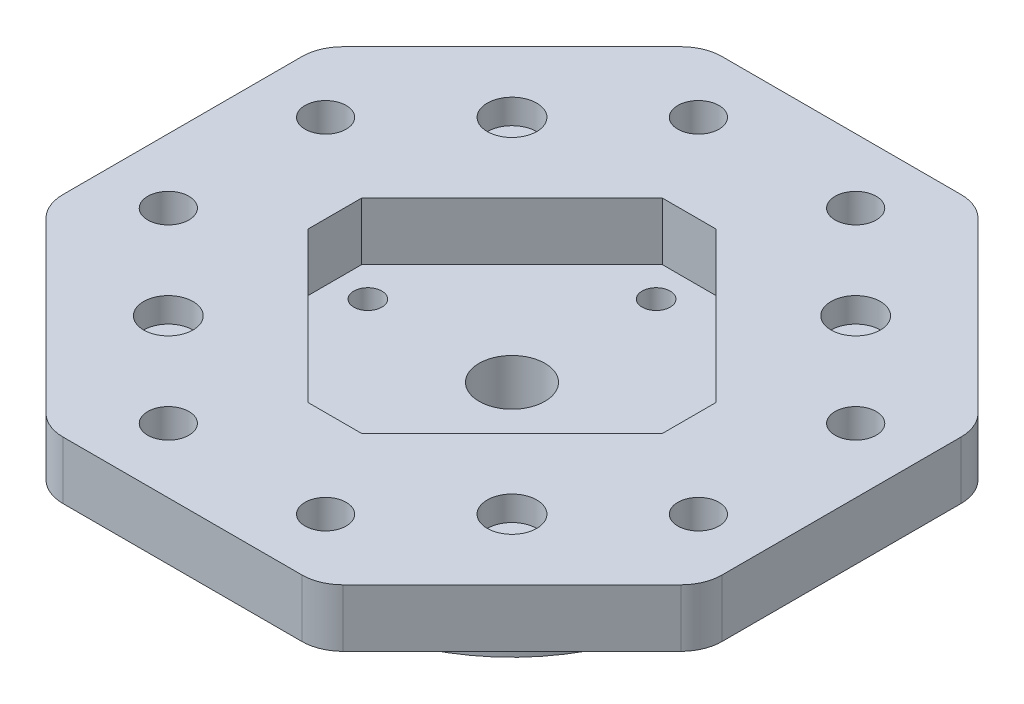
SolidWorks part; units mm, degrees
material "ABS"
ref_plane "Front" through (0, 0, 0) normal (0, 0, 1) x (1, 0, 0)
ref_plane "Top" through (0, 0, 0) normal (0, 1, 0) x (1, 0, 0)
ref_plane "Right" through (0, 0, 0) normal (1, 0, 0) x (0, 0, -1)
sketch "草图1" plane through (0, 0, 0) normal (0, 1, 0) x (1, 0, 0)
  circle A0 centre (0, 0) radius 27.5
  dimension "D1" = 55
extrude "凸台-拉伸1" add sketch "草图1" against normal blind 3
sketch "草图2" plane through (0, -3, 0) normal (0, -1, 0) x (1, 0, 0)
  circle A0 centre (0, 0) radius 22.5
  dimension "D1" = 45
extrude "凸台-拉伸2" add sketch "草图2" along normal blind 10
sketch "草图3" plane through (0, -13, 0) normal (0, -1, 0) x (1, 0, 0)
  circle A0 centre (0, 17.5) radius 1.7
  circle A1 centre (17.5, 0) radius 1.7
  circle A2 centre (0, -17.5) radius 1.7
  circle A3 centre (-17.5, 0) radius 1.7
  circle A4 centre (0, 0) radius 4
  point P12 (0, 0)
  dimension "D1" = 3.4
  dimension "D4" = 8
  dimension "D2" = 17.5
  dimension "D3" = 4
extrude "切除-拉伸1" cut sketch "草图3" against normal up to next
sketch "草图4" plane through (0, 0, 0) normal (0, 1, 0) x (1, 0, 0)
  line L0 (-66.0793, 0) -> (64.6468, 0) construction
  line L1 (0, 69.9547) -> (0, -71.394) construction
  line L2 (0, 21.5) -> (3.2487, 21.5)
  line L3 (3.2487, 21.5) -> (21.5, 3.2487)
  line L4 (21.5, 3.2487) -> (21.5, 0)
  line L5 (21.5, 0) -> (21.5, -3.2487)
  line L6 (21.5, -3.2487) -> (3.2487, -21.5)
  line L7 (3.2487, -21.5) -> (0, -21.5)
  line L8 (0, -21.5) -> (-3.2487, -21.5)
  line L9 (-3.2487, -21.5) -> (-21.5, -3.2487)
  line L10 (-21.5, -3.2487) -> (-21.5, 0)
  line L11 (-21.5, 0) -> (-21.5, 3.2487)
  line L12 (-21.5, 3.2487) -> (-3.2487, 21.5)
  line L13 (-3.2487, 21.5) -> (0, 21.5)
  line L18 (0, 40) -> (16.5685, 40)
  line L19 (16.5685, 40) -> (40, 16.5685)
  line L20 (40, 16.5685) -> (40, 0)
  line L21 (40, 0) -> (40, -16.5685)
  line L22 (16.5685, -40) -> (0, -40)
  line L23 (40, -16.5685) -> (16.5685, -40)
  line L24 (0, -40) -> (-16.5685, -40)
  line L25 (-40, -16.5685) -> (-40, 0)
  line L26 (-16.5685, -40) -> (-40, -16.5685)
  line L27 (-40, 0) -> (-40, 16.5685)
  line L28 (-16.5685, 40) -> (0, 40)
  line L29 (-40, 16.5685) -> (-16.5685, 40)
  circle A0 centre (0, 0) radius 27.5 construction
  point P24 (0, 0)
  point P29 (0, 0)
  point P40 (0, 0)
  dimension "D1" = 21.5
  dimension "D2" = 21.5
  dimension "D3" = 45
  dimension "D4" = 17.5
  dimension "D6" = 40
  dimension "D7" = 22.5
  dimension "D8" = 40
  dimension "D5" = 4
  dimension "D9" = 4
extrude "凸台-拉伸3" add sketch "草图4" along normal blind 7
sketch "草图6" plane through (0, 7, 0) normal (0, 1, 0) x (1, 0, 0)
  line L0 (0, 0) -> (42.1503, 42.1503) construction
  line L1 (21.5, 3.2487) -> (3.2487, 21.5) construction
  circle A0 centre (20.8597, 20.8597) radius 3
  circle A1 centre (20.8597, -20.8597) radius 3
  circle A2 centre (-20.8597, -20.8597) radius 3
  circle A3 centre (-20.8597, 20.8597) radius 3
  point P16 (0, 0)
  dimension "D1" = 6
  dimension "D2" = 12
extrude "切除-拉伸2" cut sketch "草图6" against normal blind 3
sketch "草图7" plane through (0, 7, 0) normal (0, 1, 0) x (1, 0, 0)
  line L0 (0, 0) -> (38.1237, 38.1237) construction
  line L1 (21.5, 3.2487) -> (3.2487, 21.5) construction
  line L3 (27.8626, 13.8567) -> (3.2196, 38.4997) construction
  circle A0 centre (9.5459, 32.1734) radius 2.5
  circle A1 centre (32.1734, 9.5459) radius 2.5
  circle A2 centre (32.1734, -9.5459) radius 2.5
  circle A3 centre (9.5459, -32.1734) radius 2.5
  circle A4 centre (-9.5459, -32.1734) radius 2.5
  circle A5 centre (-32.1734, -9.5459) radius 2.5
  circle A6 centre (-32.1734, 9.5459) radius 2.5
  circle A7 centre (-9.5459, 32.1734) radius 2.5
  point P24 (0, 0)
  dimension "D1" = 5
  dimension "D2" = 5
  dimension "D3" = 16
  dimension "D4" = 16
  dimension "D5" = 12
extrude "切除-拉伸3" cut sketch "草图7" against normal up to next
fillet "圆角1" radius 5 8 edges at (-40, 3.5, -16.5685) (-16.5685, 3.5, -40) (16.5685, 3.5, -40) (40, 3.5, -16.5685) (40, 3.5, 16.5685) (16.5685, 3.5, 40) (-40, 3.5, 16.5685) (-16.5685, 3.5, 40)
